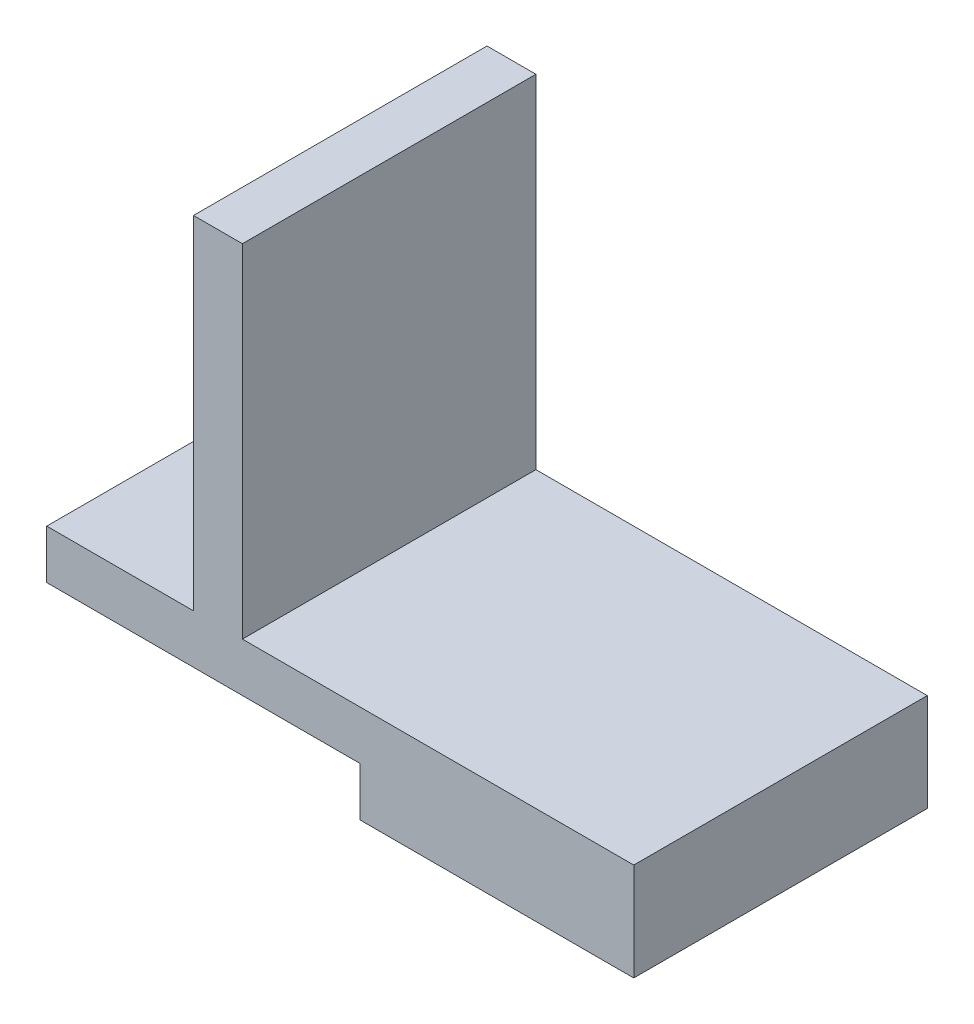
SolidWorks part; units mm, degrees
ref_plane "Front Plane" through (0, 0, 0) normal (0, 0, 1) x (1, 0, 0)
ref_plane "Top Plane" through (0, 0, 0) normal (0, 1, 0) x (1, 0, 0)
ref_plane "Right Plane" through (0, 0, 0) normal (1, 0, 0) x (0, 0, -1)
sketch "Sketch1" plane through (0, 0, 0) normal (0, 0, 1) x (1, 0, 0)
  line L0 (0, 0) -> (50.8, 0)
  line L1 (50.8, 0) -> (50.8, -12.7)
  line L2 (50.8, -12.7) -> (15.24, -12.7)
  line L3 (-25.4, -6.35) -> (-25.4, 0)
  line L4 (-25.4, 0) -> (-6.35, 0)
  line L5 (-6.35, 0) -> (-6.35, 44.45)
  line L6 (-6.35, 44.45) -> (0, 44.45)
  line L7 (0, 44.45) -> (0, 0)
  line L8 (15.24, -12.7) -> (15.24, -6.35)
  line L9 (15.24, -6.35) -> (-25.4, -6.35)
  dimension "D1" = 50.8
  dimension "D2" = 44.45
  dimension "D3" = 12.7
  dimension "D4" = 19.05
  dimension "D5" = 6.35
  dimension "D6" = 6.35
  dimension "D7" = 40.64
extrude "Boss-Extrude1" add sketch "Sketch1" along normal blind 38.1
hole_wizard "1/4 (0.25) Diameter Hole1" positions "Sketch4" profile "Sketch3" hole size "1/4" standard "ANSI Inch" end condition through all
sketch "Sketch4" plane through (0, 0, 0) normal (0, 1, 0) x (1, 0, 0)
  line L0 (-6.35, 0) -> (-25.4, 0) construction
  point P0 (-15.875, -19.05)
  point P5 (-15.875, 0)
sketch "Sketch3" plane through (-15.875, 0, 19.05) normal (1, 0, 0) x (0, 0, 1)
  line L0 (0, 0) -> (0, 12.7)
  line L1 (0, 12.7) -> (3.175, 12.7)
  line L2 (3.175, 12.7) -> (3.175, 0.635)
  line L3 (3.175, 0.635) -> (3.81, 0)
  line L5 (3.81, 0) -> (0, 0)
  line L6 (-3.175, 0.635) -> (-3.81, 0) construction
  line L11 (0, -6.35) -> (0, 107.95) construction
  dimension "Thru Hole Dia." = 6.35
  dimension "Thru Hole Depth" = 12.7
  dimension "Near C'Sink Dia." = 7.62
  dimension "Near C'Sink Angle" = 90
